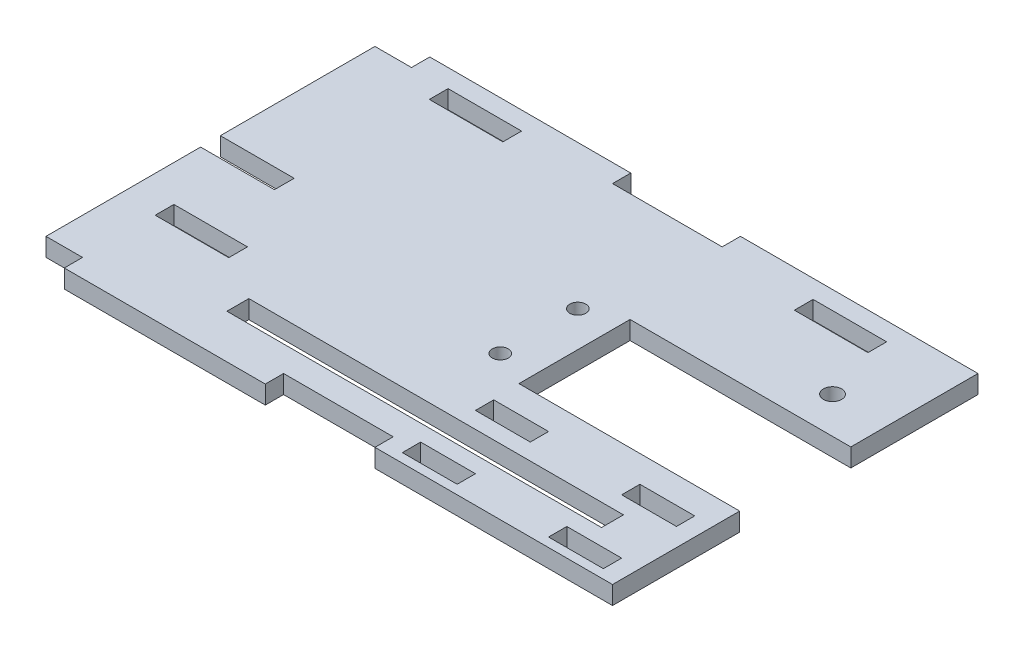
SolidWorks part; units mm, degrees
ref_plane "Front Plane" through (0, 0, 0) normal (0, 0, 1) x (1, 0, 0)
ref_plane "Top Plane" through (0, 0, 0) normal (0, 1, 0) x (1, 0, 0)
ref_plane "Right Plane" through (0, 0, 0) normal (1, 0, 0) x (0, 0, -1)
sketch "Sketch1" plane through (0, 0, 0) normal (0, 1, 0) x (1, 0, 0)
  line L0 (0, 63.5) -> (203.2, 63.5) construction
  line L1 (0, 0) -> (203.2, 0)
  line L2 (0, 0) -> (0, 60.071)
  line L3 (0, 127) -> (203.2, 127)
  line L4 (203.2, 0) -> (203.2, 44.196)
  line L5 (202.946, 82.55) -> (126.746, 82.55) construction
  line L7 (202.946, 44.45) -> (126.746, 44.45) construction
  line L8 (126.746, 82.55) -> (126.746, 44.45) construction
  line L9 (203.2, 82.804) -> (126.492, 82.804)
  line L10 (126.492, 82.804) -> (126.492, 44.196)
  line L11 (203.2, 44.196) -> (126.492, 44.196)
  line L12 (203.2, 60.579) -> (203.2, 53.721)
  line L13 (0, 66.929) -> (25.654, 66.929)
  line L14 (0, 66.675) -> (25.4, 66.675) construction
  line L16 (0, 60.325) -> (25.4, 60.325) construction
  line L17 (25.4, 66.675) -> (25.4, 60.325) construction
  line L22 (25.654, 66.929) -> (25.654, 60.071)
  line L23 (0, 60.071) -> (25.654, 60.071)
  line L27 (0, 66.929) -> (0, 127)
  line L28 (203.2, 82.804) -> (203.2, 127)
  line L29 (203.2, 53.721) -> (203.2, 60.579)
  line L30 (203.2, 82.804) -> (203.2, 44.196) construction
  line L31 (202.946, 82.55) -> (202.946, 44.45) construction
  dimension "D1" = 203.2
  dimension "D2" = 127
  dimension "D4" = 38.1
  dimension "D5" = 76.2
  dimension "D9" = 25.4
  dimension "D10" = 6.35
  dimension "D6" = 0.254
  dimension "D11" = 0.254
extrude "Boss-Extrude1" add sketch "Sketch1" along normal blind 6.35 contours L28 L3 L27 L13 L22 L23 L2 L1 L4 L11 L10 L9 region at (94.0263, 0, -63.5)
sketch "Sketch4" plane through (0, 6.35, 0) normal (0, 1, 0) x (1, 0, 0)
  line L1 (25.4762, 6.4262) -> (50.8762, 6.4262) construction
  line L2 (25.4762, 6.4262) -> (25.4762, 12.7762) construction
  line L3 (25.4762, 12.7762) -> (50.8762, 12.7762) construction
  line L4 (50.8762, 6.4262) -> (50.8762, 12.7762) construction
  line L6 (101.6, 0) -> (101.6, 127) construction
  line L8 (0, 63.5) -> (196.85, 63.5) construction
  line L9 (0, 66.929) -> (0, 60.071)
  line L16 (152.3238, 6.4262) -> (152.3238, 12.7762) construction
  line L17 (177.7238, 12.7762) -> (152.3238, 12.7762) construction
  line L18 (177.7238, 6.4262) -> (177.7238, 12.7762) construction
  line L19 (177.7238, 6.4262) -> (152.3238, 6.4262) construction
  line L20 (177.7238, 120.5738) -> (152.3238, 120.5738) construction
  line L21 (177.7238, 120.5738) -> (177.7238, 114.2238) construction
  line L22 (177.7238, 114.2238) -> (152.3238, 114.2238) construction
  line L23 (152.3238, 120.5738) -> (152.3238, 114.2238) construction
  line L24 (50.8762, 120.5738) -> (50.8762, 114.2238) construction
  line L25 (25.4762, 114.2238) -> (50.8762, 114.2238) construction
  line L26 (25.4762, 120.5738) -> (25.4762, 114.2238) construction
  line L27 (25.4762, 120.5738) -> (50.8762, 120.5738) construction
  line L28 (50.9524, 120.65) -> (50.9524, 114.1476)
  line L29 (25.4, 114.1476) -> (50.9524, 114.1476)
  line L30 (25.4, 120.65) -> (25.4, 114.1476)
  line L31 (25.4, 120.65) -> (50.9524, 120.65)
  line L32 (177.8, 120.65) -> (152.2476, 120.65)
  line L33 (152.2476, 120.65) -> (152.2476, 114.1476)
  line L34 (177.8, 114.1476) -> (152.2476, 114.1476)
  line L35 (177.8, 120.65) -> (177.8, 114.1476)
  line L36 (25.4, 6.35) -> (50.9524, 6.35) construction
  line L37 (50.9524, 6.35) -> (50.9524, 12.8524) construction
  line L38 (25.4, 12.8524) -> (50.9524, 12.8524) construction
  line L39 (25.4, 6.35) -> (25.4, 12.8524) construction
  line L40 (152.2476, 6.35) -> (152.2476, 12.8524) construction
  line L41 (177.8, 12.8524) -> (152.2476, 12.8524) construction
  line L42 (177.8, 6.35) -> (177.8, 12.8524) construction
  line L43 (177.8, 6.35) -> (152.2476, 6.35) construction
  line L44 (12.7, 127) -> (12.7, 120.65)
  line L45 (0, 0) -> (12.7, 0)
  line L46 (0, 0) -> (0, 6.35)
  line L47 (0, 6.35) -> (12.7, 6.35)
  line L48 (12.7, 0) -> (12.7, 6.35)
  line L49 (82.55, 0) -> (120.65, 0)
  line L50 (82.55, 0) -> (82.55, 6.35)
  line L51 (82.55, 6.35) -> (120.65, 6.35)
  line L52 (120.65, 0) -> (120.65, 6.35)
  line L53 (0, 120.65) -> (12.7, 120.65)
  line L54 (0, 127) -> (0, 120.65)
  line L55 (0, 127) -> (12.7, 127)
  line L56 (120.65, 127) -> (120.65, 120.65)
  line L57 (82.55, 120.65) -> (120.65, 120.65)
  line L58 (82.55, 127) -> (82.55, 120.65)
  line L59 (82.55, 127) -> (120.65, 127)
  line L60 (0, 66.929) -> (25.654, 66.929) construction
  line L61 (0, 60.071) -> (25.654, 60.071) construction
  line L62 (0, 0) -> (0, 60.071) construction
  line L63 (0, 0) -> (203.2, 0) construction
  dimension "D2" = 25.4
  dimension "D3" = 6.35
  dimension "D8" = 6.35
  dimension "D9" = 12.7
  dimension "D10" = 6.35
  dimension "D11" = 6.35
  dimension "D12" = 38.1
  dimension "D13" = 25.4
  dimension "D4" = 0.0762
  dimension "D5" = 0.0762
  dimension "D6" = 0.0762
  dimension "D7" = 0.0762
extrude "Cut-Extrude1" cut sketch "Sketch4" against normal through all contours L53 L44 | L31 L30 L29 L28 | L58 L57 L56 | L35 L32 L33 L34 | L43 L42 L41 L40 | L52 L51 L50 | L39 L36 L37 L38 | L48 L47 region at (38.1762, 6.35, -117.3988) region at (165.0238, 6.35, -117.3988) region at (6.35, 6.35, -123.825) region at (6.35, 6.35, -3.175) region at (101.6, 6.35, -3.175) region at (101.6, 6.35, -123.825)
sketch "Sketch5" plane through (0, 6.35, 0) normal (0, 1, 0) x (1, 0, 0)
  line L0 (203.2, 82.804) -> (126.492, 82.804) construction
  line L25 (203.2, 127) -> (120.65, 127)
  line L26 (120.65, 127) -> (120.65, 120.65)
  line L27 (120.65, 120.65) -> (82.55, 120.65)
  line L28 (82.55, 120.65) -> (82.55, 127)
  line L29 (82.55, 127) -> (12.7, 127)
  line L30 (12.7, 127) -> (12.7, 120.65)
  line L31 (12.7, 120.65) -> (0, 120.65)
  line L32 (0, 120.65) -> (0, 66.929)
  line L33 (0, 66.929) -> (25.654, 66.929)
  line L34 (25.654, 66.929) -> (25.654, 60.071)
  line L35 (25.654, 60.071) -> (0, 60.071)
  line L36 (0, 60.071) -> (0, 6.35)
  line L37 (0, 6.35) -> (12.7, 6.35)
  line L38 (12.7, 6.35) -> (12.7, 0)
  line L39 (12.7, 0) -> (82.55, 0)
  line L40 (82.55, 0) -> (82.55, 6.35)
  line L41 (82.55, 6.35) -> (120.65, 6.35)
  line L42 (120.65, 6.35) -> (120.65, 0)
  line L43 (120.65, 0) -> (203.2, 0)
  line L44 (203.2, 0) -> (203.2, 44.196)
  line L45 (203.2, 44.196) -> (126.492, 44.196)
  line L46 (126.492, 44.196) -> (126.492, 82.804)
  line L47 (126.492, 82.804) -> (203.2, 82.804)
  line L48 (203.2, 82.804) -> (203.2, 127)
  line L49 (203.2, 127) -> (120.65, 127) construction
  line L50 (120.65, 127) -> (120.65, 120.65) construction
  line L51 (120.65, 120.65) -> (82.55, 120.65) construction
  line L52 (82.55, 120.65) -> (82.55, 127) construction
  line L53 (82.55, 127) -> (12.7, 127) construction
  line L54 (12.7, 127) -> (12.7, 120.65) construction
  line L55 (12.7, 120.65) -> (0, 120.65) construction
  line L56 (0, 120.65) -> (0, 66.929) construction
  line L57 (0, 66.929) -> (25.654, 66.929) construction
  line L58 (25.654, 66.929) -> (25.654, 60.071) construction
  line L59 (25.654, 60.071) -> (0, 60.071) construction
  line L60 (0, 60.071) -> (0, 6.35) construction
  line L61 (0, 6.35) -> (12.7, 6.35) construction
  line L62 (12.7, 6.35) -> (12.7, 0) construction
  line L63 (12.7, 0) -> (82.55, 0) construction
  line L64 (82.55, 0) -> (82.55, 6.35) construction
  line L65 (82.55, 6.35) -> (120.65, 6.35) construction
  line L66 (120.65, 6.35) -> (120.65, 0) construction
  line L67 (120.65, 0) -> (203.2, 0) construction
  line L68 (203.2, 0) -> (203.2, 44.196) construction
  line L69 (203.2, 44.196) -> (126.492, 44.196) construction
  line L70 (126.492, 44.196) -> (126.492, 82.804) construction
  line L71 (126.492, 82.804) -> (203.2, 82.804) construction
  line L72 (203.2, 82.804) -> (203.2, 127) construction
  circle A0 centre (184.15, 95.504) radius 3.175
  dimension "D4" = 6.35
  dimension "D1" = 12.7
  dimension "D3" = 19.05
  dimension "D2" = 0
extrude "Cut-Extrude2" cut sketch "Sketch5" against normal through all
sketch "Sketch6" plane through (0, 0, 0) normal (0, -1, 0) x (1, 0, 0)
  line L0 (180.8055, 0) -> (180.8055, -127) construction
  line L1 (120.65, 0) -> (203.2, 0) construction
  line L2 (120.65, -127) -> (203.2, -127) construction
  line L3 (180.8055, -63.5) -> (71.8356, -63.5) construction
  circle A0 centre (114.173, -50.038) radius 2.7781
  circle A1 centre (114.173, -50.038) radius 2.54 construction
  circle A2 centre (114.173, -76.962) radius 2.7781
  dimension "D1" = 5.5562
extrude "Cut-Extrude3" cut sketch "Sketch6" against normal through all
sketch "Sketch7" plane through (0, 6.35, 0) normal (0, 1, 0) x (1, 0, 0)
  line L0 (0, 6.35) -> (0, 60.071) construction
  line L1 (12.7, 38.1) -> (38.1, 38.1) construction
  line L2 (12.7, 38.1) -> (12.7, 31.75) construction
  line L3 (12.7, 31.75) -> (38.1, 31.75) construction
  line L4 (38.1, 38.1) -> (38.1, 31.75) construction
  line L5 (0, 6.35) -> (12.7, 6.35) construction
  line L6 (12.6238, 38.1762) -> (38.1762, 38.1762)
  line L7 (38.1762, 38.1762) -> (38.1762, 31.6738)
  line L8 (12.6238, 31.6738) -> (38.1762, 31.6738)
  line L9 (12.6238, 38.1762) -> (12.6238, 31.6738)
  dimension "D1" = 6.35
  dimension "D2" = 25.4
  dimension "D3" = 12.7
  dimension "D4" = 25.4
  dimension "D5" = 0.0762
extrude "Cut-Extrude4" cut sketch "Sketch7" against normal through all
sketch "Sketch8" plane through (0, 0, 0) normal (0, -1, 0) x (1, 0, 0)
  line L0 (120.65, 0) -> (203.2, 0) construction
  line L1 (196.85, -3.175) -> (177.8, -3.175)
  line L2 (196.85, -3.175) -> (196.85, -9.525)
  line L3 (196.85, -9.525) -> (177.8, -9.525)
  line L4 (177.8, -3.175) -> (177.8, -9.525)
  line L5 (203.2, 0) -> (203.2, -44.196) construction
  line L6 (153.8168, -19.05) -> (177.8, -19.05) construction
  line L7 (177.8, -34.925) -> (177.8, -28.575)
  line L8 (196.85, -28.575) -> (177.8, -28.575)
  line L9 (196.85, -34.925) -> (196.85, -28.575)
  line L10 (196.85, -34.925) -> (177.8, -34.925)
  line L11 (161.925, -4.0278) -> (161.925, -32.1047) construction
  line L12 (127, -34.925) -> (146.05, -34.925)
  line L13 (127, -34.925) -> (127, -28.575)
  line L14 (127, -28.575) -> (146.05, -28.575)
  line L15 (146.05, -34.925) -> (146.05, -28.575)
  line L16 (146.05, -3.175) -> (146.05, -9.525)
  line L17 (127, -9.525) -> (146.05, -9.525)
  line L18 (127, -3.175) -> (127, -9.525)
  line L19 (127, -3.175) -> (146.05, -3.175)
  dimension "D1" = 3.175
  dimension "D2" = 6.35
  dimension "D3" = 6.35
  dimension "D4" = 19.05
  dimension "D5" = 9.525
  dimension "D6" = 31.75
extrude "Cut-Extrude5" cut sketch "Sketch8" against normal through all both and the other way through all
sketch "Sketch9" plane through (0, 0, 0) normal (0, -1, 0) x (1, 0, 0)
  line L1 (184.15, -15.24) -> (53.975, -15.24)
  line L2 (184.15, -15.24) -> (184.15, -22.86)
  line L3 (184.15, -22.86) -> (53.975, -22.86)
  line L4 (53.975, -15.24) -> (53.975, -22.86)
  line L5 (184.15, -19.05) -> (175.5768, -19.05) construction
  line L6 (196.85, -9.525) -> (177.8, -9.525) construction
  line L7 (177.8, -28.575) -> (196.85, -28.575) construction
  line L8 (196.85, -3.175) -> (196.85, -9.525) construction
  dimension "D1" = 7.62
  dimension "D2" = 130.175
  dimension "D3" = 12.7
extrude "Cut-Extrude6" cut sketch "Sketch9" against normal through all both and the other way through all
